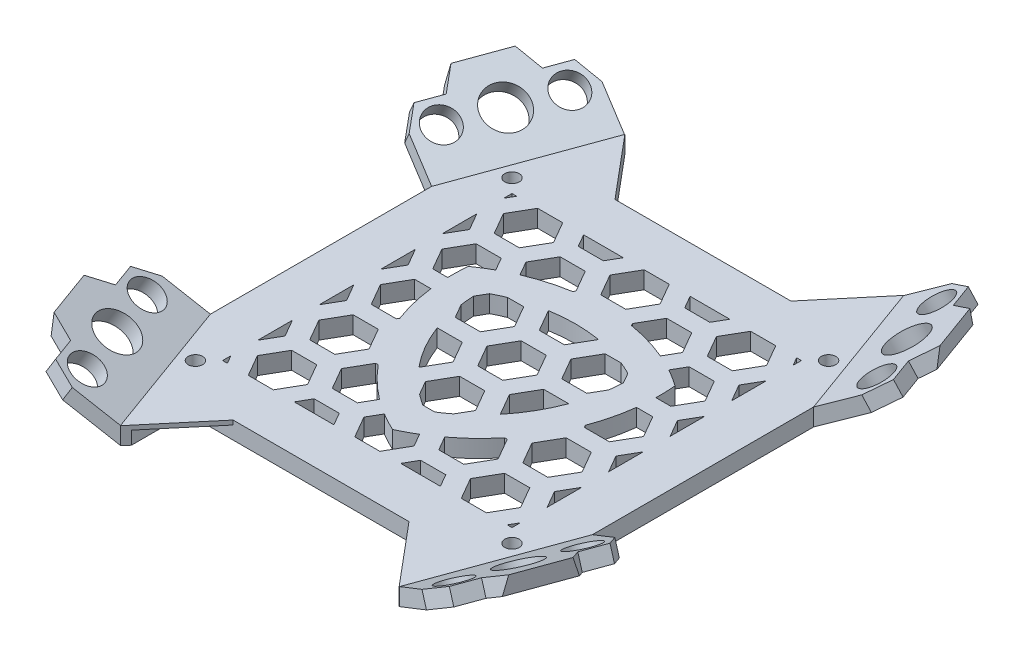
SolidWorks part; units mm, degrees
ref_plane "Front Plane" through (0, 0, 0) normal (0, 0, 1) x (1, 0, 0)
ref_plane "Top Plane" through (0, 0, 0) normal (0, 1, 0) x (1, 0, 0)
ref_plane "Right Plane" through (0, 0, 0) normal (1, 0, 0) x (0, 0, -1)
sketch "Sketch11" plane through (0, 0, 0) normal (0, 1, 0) x (1, 0, 0)
  line L0 (-50, -50) -> (-50, 50)
  line L1 (-30.4059, -66) -> (30.4059, -66)
  line L2 (-66, -38.2239) -> (-66, 0)
  line L3 (-30.4059, 66) -> (30.4059, 66)
  line L4 (66, -38.2239) -> (66, 38.2239)
  line L5 (-66, -66) -> (66, 66) construction
  line L6 (-50, 50) -> (66, -66) construction
  line L7 (-50, 50) -> (50, 50)
  line L8 (50, -50) -> (50, 50)
  line L9 (-50, -50) -> (50, -50)
  line L18 (-66, 0) -> (-66, 38.2239) construction
  line L19 (-66, -66) -> (-66, 66) construction
  line L20 (66, 38.2239) -> (66, 66) construction
  line L21 (66, -66) -> (66, 66) construction
  line L22 (66, -66) -> (66, -38.2239) construction
  line L23 (-66, -66) -> (-66, -38.2239) construction
  line L24 (-48.1804, 87.1828) -> (-65.9654, 38.3188)
  line L27 (-48.1804, 87.1828) -> (-30.4059, 66)
  line L28 (-66, 38.2239) -> (-66, 66) construction
  line L29 (-66, 66) -> (66, 66) construction
  line L30 (0, -55) -> (0, 55) construction
  line L31 (48.1804, 87.1828) -> (30.4059, 66)
  line L32 (65.9654, 38.3188) -> (66, 38.2239)
  line L33 (48.1804, 87.1828) -> (65.9654, 38.3188)
  line L34 (-55, 0) -> (55, 0) construction
  line L35 (65.9654, -38.3188) -> (66, -38.2239)
  line L36 (48.1804, -87.1828) -> (65.9654, -38.3188)
  line L37 (48.1804, -87.1828) -> (30.4059, -66)
  line L38 (-48.1804, -87.1828) -> (-30.4059, -66)
  line L39 (-65.9654, -38.3188) -> (-66, -38.2239)
  line L40 (-48.1804, -87.1828) -> (-65.9654, -38.3188)
  line L41 (30.4059, 66) -> (66, 66) construction
  line L42 (30.4059, -66) -> (66, -66) construction
  line L43 (-66, -66) -> (66, -66) construction
  line L44 (-66, -66) -> (-30.4059, -66) construction
  line L45 (-66, 66) -> (-30.4059, 66) construction
  line L46 (-57.0729, 62.7508) -> (-66, 66) construction
  line L47 (-66, 38.2239) -> (-66, 0)
  line L48 (-66, 38.2239) -> (-65.9654, 38.3188)
  point P0 (0, 0)
  dimension "D1" = 132
  dimension "D2" = 9.5
  dimension "D4" = 52
  dimension "D5" = 60
  dimension "D8" = 20
  dimension "D3" = 16
extrude "Boss-Extrude6" add sketch "Sketch11" along normal blind 6
ref_plane "Plane1" through (4.5644, 0, -12.5405) normal (0.342, 0, -0.9397) x (0, -1, 0)
sketch "Sketch12" plane through (4.5644, 0, -12.5405) normal (0.342, 0, -0.9397) x (0, -1, 0)
  line L0 (-6, 75.093) -> (-21, 101.0738)
  line L1 (-21, 101.0738) -> (-15, 101.0738)
  line L2 (-15, 101.0738) -> (0, 75.093)
  line L4 (-6, 75.093) -> (0, 75.093)
  dimension "D1" = 6
  dimension "D2" = 30
  dimension "D3" = 60
extrude "Boss-Extrude7" add sketch "Sketch12" along normal blind 52
sketch "Sketch13" plane through (-15.1997, -28.0162, -5.5322) normal (0.4698, 0.866, 0.171) x (0.8827, -0.4609, -0.091)
  line L0 (-51.2289, 92.4122) -> (-71.3763, 44.4738) construction
  line L1 (-65.0573, 98.2239) -> (-37.4005, 86.6004) construction
  line L2 (-85.2046, 50.2856) -> (-57.5479, 38.6621) construction
  line L3 (-65.0573, 98.2239) -> (-85.2046, 50.2856) construction
  line L5 (-71.7755, 82.2385) -> (-85.1655, 50.3787) construction
  line L6 (-78.4863, 66.2709) -> (-73.2618, 59.3889)
  line L15 (-73.2618, 59.3889) -> (-76.6247, 51.3873)
  line L16 (-76.6247, 51.3873) -> (-71.3763, 44.4738)
  line L17 (-51.2289, 92.4122) -> (-59.8399, 91.3237)
  line L24 (-71.7755, 82.2385) -> (-63.2027, 83.3222)
  line L25 (-63.2027, 83.3222) -> (-59.8399, 91.3237)
  line L37 (-71.3763, 44.4738) -> (-85.2046, 50.2856)
  line L38 (-85.2046, 50.2856) -> (-78.4863, 66.2709)
  line L39 (-71.7755, 82.2385) -> (-65.0573, 98.2239)
  line L40 (-65.0573, 98.2239) -> (-51.2289, 92.4122)
  line L41 (-85.1655, 50.3787) -> (-78.4863, 66.2709) construction
  line L49 (-44.1188, 70.6151) -> (-49.3553, 77.5128) [skipped]
  line L51 (-60.0486, 83.7209) -> (-71.7755, 82.2385) [skipped]
  line L52 (-81.8532, 58.3033) -> (-86.159, 57.7591) construction
  line L53 (-54.1654, 46.6668) -> (-56.7896, 50.1235) construction
  line L54 (-62.7648, 45.5623) -> (-61.0832, 49.5633) [skipped]
  line L55 (-71.3763, 44.4738) -> (-62.7648, 45.5623) [skipped]
  line L56 (-68.0134, 52.4754) -> (-62.5566, 53.1651) construction
  line L57 (-50.8296, 54.6474) -> (-44.1188, 70.6151) [skipped]
  circle A0 centre (-68.0132, 52.4758) radius 5.5
  circle A1 centre (-61.3026, 68.443) radius 7
  circle A2 centre (-54.592, 84.4101) radius 5.5
  dimension "D1" = 11
  dimension "D2" = 11
  dimension "D3" = 14
  dimension "D6" = 17.3397
  dimension "D4" = 17.32
  dimension "D5" = 17.32
  dimension "D7" = 17.3397
  dimension "D8" = 120
  dimension "D9" = 30
  dimension "D10" = 7.4833
  dimension "D11" = 30
extrude "Cut-Extrude1" cut sketch "Sketch13" against normal through all
mirror "Mirror3" about plane through (0, 0, 0) normal (1, 0, 0) of "Cut-Extrude1", "Boss-Extrude7"
mirror "Mirror4" about plane through (0, 0, 0) normal (0, 0, 1) of "Boss-Extrude7", "Cut-Extrude1", "Mirror3"
sketch "Sketch18" plane through (0, 0, 66) normal (0, 0, 1) x (1, 0, 0)
  line L0 (0, 6) -> (0, 0) construction
  line L1 (-30.4059, 6) -> (30.4059, 6) construction
  line L2 (-30.4059, 0) -> (30.4059, 0) construction
  line L3 (0, 4.5) -> (-46.4059, 4.5)
  line L4 (-46.4059, 4.5) -> (-46.4059, 0)
  line L6 (-46.4059, 0) -> (46.4059, 0)
  line L7 (30.4059, 0) -> (48.1804, 0) construction
  line L8 (46.4059, 0) -> (46.4059, 4.5)
  line L9 (46.4059, 4.5) -> (0, 4.5)
  line L11 (-30.4059, 6) -> (-30.4059, 0) construction
  line L12 (30.4059, 6) -> (30.4059, 0) construction
  line L13 (-48.1804, 0) -> (-30.4059, 0) construction
  dimension "D1" = 16
  dimension "D2" = 16
  dimension "D3" = 1.5
extrude "Cut-Extrude2" cut sketch "Sketch18" along normal through all
sketch "Sketch19" plane through (0, 6, 0) normal (0, 1, 0) x (1, 0, 0)
  line L0 (30.4059, 66) -> (-30.4059, 66) construction
  line L3 (-66, 38.2239) -> (-66, -38.2239) construction
  line L4 (66, -38.2239) -> (66, 38.2239) construction
  circle A0 centre (-54.7, 54.7) radius 2.5
  circle A1 centre (54.7, 54.7) radius 2.5
  circle A2 centre (54.7, -54.7) radius 2.5
  circle A3 centre (-54.7, -54.7) radius 2.5
  point P15 (0, 0)
  dimension "D1" = 5
  dimension "D2" = 11.3
  dimension "D3" = 11.3
  dimension "D5" = 11.3
  dimension "D6" = 11.3
  dimension "D4" = 4
extrude "Cut-Extrude3" cut sketch "Sketch19" against normal through all
sketch "Sketch20" plane through (0, 0, 0) normal (0, 1, 0) x (1, 0, 0)
  line L0 (0, 0) -> (0, -28.75) construction
  line L1 (0, 0) -> (-25.9808, 15) construction
  line L2 (0, 0) -> (24.8982, 14.375) construction
  line L3 (8.6603, 21.25) -> (4.3301, 28.75) construction
  line L4 (8.6603, 0) -> (4.3301, 7.5)
  line L5 (4.3301, 7.5) -> (-4.3301, 7.5)
  line L6 (-4.3301, 7.5) -> (-8.6603, 0)
  line L7 (-8.6603, 0) -> (-4.3301, -7.5)
  line L8 (-4.3301, -7.5) -> (4.3301, -7.5)
  line L9 (4.3301, -7.5) -> (8.6603, 0)
  line L10 (4.3301, 28.75) -> (-4.3301, 28.75) construction
  line L11 (-4.3301, 28.75) -> (-8.6603, 21.25) construction
  line L12 (-8.6522, 21.2361) -> (-4.3301, 13.75)
  line L13 (-4.3301, 13.75) -> (4.3301, 13.75)
  line L14 (4.3301, 13.75) -> (8.6522, 21.2361)
  line L15 (8.6603, 42.5) -> (4.3301, 50)
  line L16 (4.3301, 50) -> (-4.3301, 50)
  line L17 (-4.3301, 50) -> (-8.6603, 42.5)
  line L18 (-8.6603, 42.5) -> (-4.3301, 35)
  line L19 (-4.3301, 35) -> (4.3301, 35)
  line L20 (4.3301, 35) -> (8.6603, 42.5)
  line L21 (-11.55, 0) -> (11.55, 0) construction
  line L22 (4.3301, -13.75) -> (8.6603, -21.25)
  line L23 (-4.3301, -13.75) -> (4.3301, -13.75)
  line L24 (-8.6603, -21.25) -> (-4.3301, -13.75)
  line L25 (-5.899, -26.0327) -> (-8.6603, -21.25)
  line L26 (2.0538, -28.75) -> (-2.0538, -28.75)
  line L27 (8.6603, -21.25) -> (5.899, -26.0327)
  line L28 (6.0762, -38.0243) -> (8.6603, -42.5)
  line L29 (-4.3301, -35) -> (4.3301, -35) construction
  line L30 (-8.6603, -42.5) -> (-6.0762, -38.0243)
  line L31 (-4.3301, -50) -> (-8.6603, -42.5)
  line L32 (4.3301, -50) -> (-4.3301, -50)
  line L33 (8.6603, -42.5) -> (4.3301, -50)
  line L34 (4.3301, -7.5) -> (4.3301, -13.75) construction
  line L35 (4.3301, -10.625) -> (18.403, -10.625) construction
  line L36 (11.2674, -34.5157) -> (14.0729, -39.375)
  line L37 (9.7428, -10.625) -> (14.0649, -18.1111)
  line L38 (18.403, -18.125) -> (22.7332, -18.125) construction
  line L39 (22.7332, -18.125) -> (24.8982, -14.375) construction
  line L40 (24.8982, -6.875) -> (22.7332, -3.125) construction
  line L41 (22.7171, -3.125) -> (14.0729, -3.125)
  line L42 (14.0729, -3.125) -> (9.7428, -10.625)
  line L43 (14.0729, -39.375) -> (22.7332, -39.375)
  line L44 (22.7332, -39.375) -> (27.0633, -31.875)
  line L45 (27.0633, -31.875) -> (22.7332, -24.375)
  line L46 (22.7332, -24.375) -> (21.8611, -24.375)
  line L47 (14.0729, -24.375) -> (9.7428, -31.875) construction
  line L48 (9.7428, -53.125) -> (14.0729, -60.625) construction
  line L49 (14.0729, -60.625) -> (22.7332, -60.625) construction
  line L50 (22.7332, -60.625) -> (27.0633, -53.125) construction
  line L51 (25.2591, -50) -> (22.7332, -45.625)
  line L52 (22.7332, -45.625) -> (14.0729, -45.625)
  line L53 (14.0729, -45.625) -> (11.547, -50)
  line L54 (14.0729, 45.625) -> (11.547, 50)
  line L55 (22.7332, 45.625) -> (14.0729, 45.625)
  line L56 (25.2591, 50) -> (22.7332, 45.625)
  line L57 (22.7332, 60.625) -> (27.0633, 53.125) construction
  line L58 (14.0729, 60.625) -> (22.7332, 60.625) construction
  line L59 (9.7428, 53.125) -> (14.0729, 60.625) construction
  line L60 (10.1788, 31.1197) -> (9.7428, 31.875)
  line L61 (22.7332, 24.375) -> (14.0729, 24.375) construction
  line L62 (27.0633, 31.875) -> (24.2578, 27.0157)
  line L63 (22.7332, 39.375) -> (27.0633, 31.875)
  line L64 (14.0729, 39.375) -> (22.7332, 39.375)
  line L65 (9.7428, 31.875) -> (14.0729, 39.375)
  line L66 (14.0729, 3.125) -> (9.7428, 10.625)
  line L67 (22.7332, 3.125) -> (14.0729, 3.125)
  line L68 (25.4945, 7.9077) -> (22.7332, 3.125)
  line L69 (23.8713, 16.1537) -> (25.9251, 12.5963)
  line L70 (14.0729, 18.125) -> (19.5955, 18.125)
  line L71 (9.7428, 10.625) -> (14.0729, 18.125)
  line L72 (45.4663, 42.5) -> (41.1362, 50)
  line L73 (41.1362, 50) -> (32.476, 50)
  line L74 (32.476, 50) -> (28.1458, 42.5)
  line L75 (28.1458, 42.5) -> (32.476, 35)
  line L76 (32.476, 35) -> (41.1362, 35)
  line L77 (41.1362, 35) -> (45.4663, 42.5)
  line L78 (50, 47.1475) -> (48.3531, 50)
  line L79 (46.5489, 53.125) -> (50.879, 60.625) construction
  line L80 (50.879, 60.625) -> (59.5392, 60.625) construction
  line L81 (59.5392, 60.625) -> (63.8694, 53.125) construction
  line L82 (63.8694, 53.125) -> (59.5392, 45.625) construction
  line L83 (59.5392, 45.625) -> (50.879, 45.625) construction
  line L84 (50, 25.8975) -> (46.5489, 31.875)
  line L85 (46.5489, 31.875) -> (50, 37.8525)
  line L86 (50.879, 39.375) -> (59.5392, 39.375) construction
  line L87 (59.5392, 39.375) -> (63.8694, 31.875) construction
  line L88 (63.8694, 31.875) -> (59.5392, 24.375) construction
  line L89 (59.5392, 24.375) -> (50.879, 24.375) construction
  line L90 (45.4663, 21.25) -> (41.1362, 28.75)
  line L91 (41.1362, 28.75) -> (32.476, 28.75)
  line L92 (32.476, 28.75) -> (29.8919, 24.2743)
  line L93 (28.1458, 21.25) -> (32.476, 13.75) construction
  line L94 (35.9682, 13.75) -> (41.1362, 13.75)
  line L95 (41.1362, 13.75) -> (45.4663, 21.25)
  line L96 (50, 4.6475) -> (46.5489, 10.625)
  line L97 (46.5489, 10.625) -> (50, 16.6025)
  line L98 (50.879, 18.125) -> (59.5392, 18.125) construction
  line L99 (59.5392, 18.125) -> (63.8694, 10.625) construction
  line L100 (63.8694, 10.625) -> (59.5392, 3.125) construction
  line L101 (59.5392, 3.125) -> (50.879, 3.125) construction
  line L102 (45.4663, 0) -> (41.1362, 7.5)
  line L103 (41.1362, 7.5) -> (35.5252, 7.5)
  line L104 (32.476, 7.5) -> (28.1458, 0) construction
  line L105 (32.0399, -6.7447) -> (32.476, -7.5)
  line L106 (32.476, -7.5) -> (41.1362, -7.5)
  line L107 (41.1362, -7.5) -> (45.4663, 0)
  line L108 (41.1362, -13.75) -> (45.4663, -21.25)
  line L109 (45.4663, -21.25) -> (41.1362, -28.75)
  line L110 (41.1362, -28.75) -> (32.476, -28.75)
  line L111 (32.476, -28.75) -> (28.1458, -21.25)
  line L112 (28.1458, -21.25) -> (32.476, -13.75)
  line L113 (32.476, -13.75) -> (41.1362, -13.75)
  line L114 (46.5489, -10.625) -> (50, -16.6025)
  line L115 (50.879, -18.125) -> (59.5392, -18.125) construction
  line L116 (59.5392, -18.125) -> (63.8694, -10.625) construction
  line L117 (63.8694, -10.625) -> (59.5392, -3.125) construction
  line L118 (59.5392, -3.125) -> (50.879, -3.125) construction
  line L119 (50, -4.6475) -> (46.5489, -10.625)
  line L120 (46.5489, -31.875) -> (50, -37.8525)
  line L121 (50.879, -39.375) -> (59.5392, -39.375) construction
  line L122 (59.5392, -39.375) -> (63.8694, -31.875) construction
  line L123 (63.8694, -31.875) -> (59.5392, -24.375) construction
  line L124 (59.5392, -24.375) -> (50.879, -24.375) construction
  line L125 (50, -25.8975) -> (46.5489, -31.875)
  line L126 (41.1362, -35) -> (45.4663, -42.5)
  line L127 (45.4663, -42.5) -> (41.1362, -50)
  line L128 (41.1362, -50) -> (32.476, -50)
  line L129 (32.476, -50) -> (28.1458, -42.5)
  line L130 (28.1458, -42.5) -> (32.476, -35)
  line L131 (32.476, -35) -> (41.1362, -35)
  line L132 (46.5489, -53.125) -> (50.879, -60.625) construction
  line L133 (50.879, -60.625) -> (59.5392, -60.625) construction
  line L134 (59.5392, -60.625) -> (63.8694, -53.125) construction
  line L135 (63.8694, -53.125) -> (59.5392, -45.625) construction
  line L136 (59.5392, -45.625) -> (50.879, -45.625) construction
  line L137 (50, -47.1475) -> (48.3531, -50)
  line L138 (0, -11.55) -> (0, 11.55) construction
  line L139 (-50, -47.1475) -> (-48.3531, -50)
  line L140 (-59.5392, -45.625) -> (-50.879, -45.625) construction
  line L141 (-63.8694, -53.125) -> (-59.5392, -45.625) construction
  line L142 (-59.5392, -60.625) -> (-63.8694, -53.125) construction
  line L143 (-50.879, -60.625) -> (-59.5392, -60.625) construction
  line L144 (-46.5489, -53.125) -> (-50.879, -60.625) construction
  line L145 (-50, -25.8975) -> (-46.5489, -31.875)
  line L146 (-59.5392, -24.375) -> (-50.879, -24.375) construction
  line L147 (-63.8694, -31.875) -> (-59.5392, -24.375) construction
  line L148 (-59.5392, -39.375) -> (-63.8694, -31.875) construction
  line L149 (-50.879, -39.375) -> (-59.5392, -39.375) construction
  line L150 (-46.5489, -31.875) -> (-50, -37.8525)
  line L151 (-50, -4.6475) -> (-46.5489, -10.625)
  line L152 (-59.5392, -3.125) -> (-50.879, -3.125) construction
  line L153 (-63.8694, -10.625) -> (-59.5392, -3.125) construction
  line L154 (-59.5392, -18.125) -> (-63.8694, -10.625) construction
  line L155 (-50.879, -18.125) -> (-59.5392, -18.125) construction
  line L156 (-46.5489, -10.625) -> (-50, -16.6025)
  line L157 (-59.5392, 3.125) -> (-50.879, 3.125) construction
  line L158 (-63.8694, 10.625) -> (-59.5392, 3.125) construction
  line L159 (-59.5392, 18.125) -> (-63.8694, 10.625) construction
  line L160 (-50.879, 18.125) -> (-59.5392, 18.125) construction
  line L161 (-46.5489, 10.625) -> (-50, 16.6025)
  line L162 (-50, 4.6475) -> (-46.5489, 10.625)
  line L163 (-59.5392, 24.375) -> (-50.879, 24.375) construction
  line L164 (-63.8694, 31.875) -> (-59.5392, 24.375) construction
  line L165 (-59.5392, 39.375) -> (-63.8694, 31.875) construction
  line L166 (-50.879, 39.375) -> (-59.5392, 39.375) construction
  line L167 (-46.5489, 31.875) -> (-50, 37.8525)
  line L168 (-50, 25.8975) -> (-46.5489, 31.875)
  line L169 (-59.5392, 45.625) -> (-50.879, 45.625) construction
  line L170 (-63.8694, 53.125) -> (-59.5392, 45.625) construction
  line L171 (-59.5392, 60.625) -> (-63.8694, 53.125) construction
  line L172 (-50.879, 60.625) -> (-59.5392, 60.625) construction
  line L173 (-46.5489, 53.125) -> (-50.879, 60.625) construction
  line L174 (-50, 47.1475) -> (-48.3531, 50)
  line L175 (-41.1362, 35) -> (-45.4663, 42.5)
  line L176 (-32.476, 35) -> (-41.1362, 35)
  line L177 (-28.1458, 42.5) -> (-32.476, 35)
  line L178 (-32.476, 50) -> (-28.1458, 42.5)
  line L179 (-41.1362, 50) -> (-32.476, 50)
  line L180 (-45.4663, 42.5) -> (-41.1362, 50)
  line L181 (-41.1362, 13.75) -> (-45.4663, 21.25)
  line L182 (-35.9682, 13.75) -> (-41.1362, 13.75)
  line L183 (-28.1458, 21.25) -> (-32.476, 13.75) construction
  line L184 (-32.476, 28.75) -> (-29.8919, 24.2743)
  line L185 (-41.1362, 28.75) -> (-32.476, 28.75)
  line L186 (-45.4663, 21.25) -> (-41.1362, 28.75)
  line L187 (-41.1362, -7.5) -> (-45.4663, 0)
  line L188 (-32.476, -7.5) -> (-41.1362, -7.5)
  line L189 (-32.0399, -6.7447) -> (-32.476, -7.5)
  line L190 (-32.476, 7.5) -> (-28.1458, 0) construction
  line L191 (-41.1362, 7.5) -> (-35.5252, 7.5)
  line L192 (-45.4663, 0) -> (-41.1362, 7.5)
  line L193 (-32.476, -13.75) -> (-41.1362, -13.75)
  line L194 (-28.1458, -21.25) -> (-32.476, -13.75)
  line L195 (-32.476, -28.75) -> (-28.1458, -21.25)
  line L196 (-41.1362, -28.75) -> (-32.476, -28.75)
  line L197 (-45.4663, -21.25) -> (-41.1362, -28.75)
  line L198 (-41.1362, -13.75) -> (-45.4663, -21.25)
  line L199 (-32.476, -35) -> (-41.1362, -35)
  line L200 (-28.1458, -42.5) -> (-32.476, -35)
  line L201 (-32.476, -50) -> (-28.1458, -42.5)
  line L202 (-41.1362, -50) -> (-32.476, -50) construction
  line L203 (-45.4663, -42.5) -> (-41.1362, -50)
  line L204 (-41.1362, -35) -> (-45.4663, -42.5)
  line L205 (-14.0729, -45.625) -> (-11.547, -50)
  line L206 (-22.7332, -45.625) -> (-14.0729, -45.625)
  line L207 (-25.2591, -50) -> (-22.7332, -45.625)
  line L208 (-22.7332, -60.625) -> (-27.0633, -53.125) construction
  line L209 (-14.0729, -60.625) -> (-22.7332, -60.625) construction
  line L210 (-9.7428, -53.125) -> (-14.0729, -60.625) construction
  line L211 (-14.0729, -24.375) -> (-9.7428, -31.875) construction
  line L212 (-22.7332, -24.375) -> (-21.8611, -24.375)
  line L213 (-27.0633, -31.875) -> (-22.7332, -24.375)
  line L214 (-22.7332, -39.375) -> (-27.0633, -31.875)
  line L215 (-14.0729, -39.375) -> (-22.7332, -39.375)
  line L216 (-11.2674, -34.5157) -> (-14.0729, -39.375)
  line L217 (-14.0729, -3.125) -> (-9.7428, -10.625)
  line L218 (-22.7171, -3.125) -> (-14.0729, -3.125)
  line L219 (-27.0633, -10.625) -> (-22.7332, -3.125) construction
  line L220 (-22.7332, -18.125) -> (-27.0633, -10.625) construction
  line L221 (-14.0729, -18.125) -> (-22.7332, -18.125) construction
  line L222 (-9.7428, -10.625) -> (-14.0649, -18.1111)
  line L223 (-22.7332, 3.125) -> (-14.0729, 3.125)
  line L224 (-25.4945, 7.9077) -> (-22.7332, 3.125)
  line L225 (-23.8713, 16.1537) -> (-25.9251, 12.5963)
  line L226 (-14.0729, 18.125) -> (-19.5955, 18.125)
  line L227 (-9.7428, 10.625) -> (-14.0729, 18.125)
  line L228 (-14.0729, 3.125) -> (-9.7428, 10.625)
  line L229 (-22.7332, 24.375) -> (-14.0729, 24.375) construction
  line L230 (-27.0633, 31.875) -> (-24.2578, 27.0157)
  line L231 (-22.7332, 39.375) -> (-27.0633, 31.875)
  line L232 (-14.0729, 39.375) -> (-22.7332, 39.375)
  line L233 (-9.7428, 31.875) -> (-14.0729, 39.375)
  line L234 (-10.1788, 31.1197) -> (-9.7428, 31.875)
  line L235 (-22.7332, 45.625) -> (-14.0729, 45.625)
  line L236 (-25.2591, 50) -> (-22.7332, 45.625)
  line L237 (-22.7332, 60.625) -> (-27.0633, 53.125) construction
  line L238 (-14.0729, 60.625) -> (-22.7332, 60.625) construction
  line L239 (-9.7428, 53.125) -> (-14.0729, 60.625) construction
  line L240 (-14.0729, 45.625) -> (-11.547, 50)
  line L241 (-48.3531, 50) -> (-46.5489, 53.125) construction
  line L242 (-48.3531, 50) -> (-25.2591, 50)
  line L243 (-50, 47.1475) -> (-50, 37.8525)
  line L244 (-48.3531, -50) -> (-25.2591, -50) construction
  line L245 (50, 47.1475) -> (50, 37.8525)
  line L246 (-50.879, 45.625) -> (-50, 47.1475) construction
  line L247 (-50, 50) -> (-50, 47.1475) construction
  line L248 (-50, 50) -> (-48.3531, 50) construction
  line L249 (-50, 37.8525) -> (-50.879, 39.375) construction
  line L250 (-50.879, 24.375) -> (-50, 25.8975) construction
  line L251 (-50, 16.6025) -> (-50.879, 18.125) construction
  line L252 (-50.879, 3.125) -> (-50, 4.6475) construction
  line L253 (-50.879, -3.125) -> (-50, -4.6475) construction
  line L254 (-50, -16.6025) -> (-50.879, -18.125) construction
  line L255 (-50, 37.8525) -> (-50, 25.8975) construction
  line L256 (-50, 25.8975) -> (-50, 16.6025)
  line L257 (-50, 16.6025) -> (-50, 4.6475) construction
  line L258 (-50, 4.6475) -> (-50, -4.6475)
  line L259 (-50, -4.6475) -> (-50, -16.6025) construction
  line L260 (-50, -16.6025) -> (-50, -25.8975)
  line L261 (-50, -25.8975) -> (-50, -37.8525) construction
  line L262 (-50, -37.8525) -> (-50, -47.1475)
  line L263 (-50.879, -24.375) -> (-50, -25.8975) construction
  line L264 (-50, -37.8525) -> (-50.879, -39.375) construction
  line L265 (-50.879, -45.625) -> (-50, -47.1475) construction
  line L266 (-48.3531, -50) -> (-46.5489, -53.125) construction
  line L267 (-50, -50) -> (-48.3531, -50) construction
  line L268 (-50, -47.1475) -> (-50, -50) construction
  line L269 (-27.0633, -53.125) -> (-25.2591, -50) construction
  line L270 (-11.547, -50) -> (-9.7428, -53.125) construction
  line L271 (11.547, -50) -> (9.7428, -53.125) construction
  line L272 (27.0633, -53.125) -> (25.2591, -50) construction
  line L273 (11.547, -50) -> (25.2591, -50) construction
  line L274 (25.2591, -50) -> (48.3531, -50)
  line L275 (-25.2591, -50) -> (-11.547, -50) construction
  line L276 (-11.547, -50) -> (11.547, -50)
  line L277 (48.3531, -50) -> (46.5489, -53.125) construction
  line L278 (50.879, -45.625) -> (50, -47.1475) construction
  line L279 (50, -47.1475) -> (50, -50) construction
  line L280 (48.3531, -50) -> (50, -50) construction
  line L281 (50.879, -24.375) -> (50, -25.8975) construction
  line L282 (50, -37.8525) -> (50.879, -39.375) construction
  line L283 (50, -25.8975) -> (50, -37.8525) construction
  line L284 (50, -37.8525) -> (50, -47.1475)
  line L285 (50.879, -3.125) -> (50, -4.6475) construction
  line L286 (50, -16.6025) -> (50.879, -18.125) construction
  line L287 (50, -4.6475) -> (50, -16.6025) construction
  line L288 (50, -16.6025) -> (50, -25.8975)
  line L289 (50, 16.6025) -> (50.879, 18.125) construction
  line L290 (50.879, 3.125) -> (50, 4.6475) construction
  line L291 (50, 16.6025) -> (50, 4.6475) construction
  line L292 (50, 4.6475) -> (50, -4.6475)
  line L293 (50, 37.8525) -> (50.879, 39.375) construction
  line L294 (50.879, 24.375) -> (50, 25.8975) construction
  line L295 (50, 37.8525) -> (50, 25.8975) construction
  line L296 (50, 25.8975) -> (50, 16.6025)
  line L297 (50.879, 45.625) -> (50, 47.1475) construction
  line L298 (48.3531, 50) -> (46.5489, 53.125) construction
  line L299 (48.3531, 50) -> (50, 50) construction
  line L300 (50, 50) -> (50, 47.1475) construction
  line L301 (11.547, 50) -> (9.7428, 53.125) construction
  line L302 (27.0633, 53.125) -> (25.2591, 50) construction
  line L303 (11.547, 50) -> (25.2591, 50) construction
  line L304 (25.2591, 50) -> (48.3531, 50)
  line L305 (-11.547, 50) -> (-9.7428, 53.125) construction
  line L306 (-27.0633, 53.125) -> (-25.2591, 50) construction
  line L307 (-25.2591, 50) -> (-11.547, 50) construction
  line L308 (-11.547, 50) -> (11.547, 50)
  line L309 (-14.0729, 24.375) -> (-10.1788, 31.1197) construction
  line L310 (-24.2578, 27.0157) -> (-22.7332, 24.375) construction
  line L311 (14.0729, 24.375) -> (10.1788, 31.1197) construction
  line L312 (24.2578, 27.0157) -> (22.7332, 24.375) construction
  line L313 (29.8919, 24.2743) -> (28.1458, 21.25) construction
  line L314 (32.476, 13.75) -> (35.9682, 13.75) construction
  line L315 (35.5252, 7.5) -> (32.476, 7.5) construction
  line L316 (28.1458, 0) -> (32.0399, -6.7447) construction
  line L317 (21.8611, -24.375) -> (14.0729, -24.375) construction
  line L318 (9.7428, -31.875) -> (11.2674, -34.5157) construction
  line L319 (-6.0762, -38.0243) -> (-4.3301, -35) construction
  line L320 (4.3301, -35) -> (6.0762, -38.0243) construction
  line L321 (-21.8611, -24.375) -> (-14.0729, -24.375) construction
  line L322 (-9.7428, -31.875) -> (-11.2674, -34.5157) construction
  line L323 (-28.1458, 0) -> (-32.0399, -6.7447) construction
  line L324 (-35.5252, 7.5) -> (-32.476, 7.5) construction
  line L325 (-32.476, 13.75) -> (-35.9682, 13.75) construction
  line L326 (-29.8919, 24.2743) -> (-28.1458, 21.25) construction
  line L327 (-22.7332, 18.125) -> (-23.8713, 16.1537) construction
  line L328 (-19.5955, 18.125) -> (-22.7332, 18.125) construction
  line L329 (-25.9251, 12.5963) -> (-27.0633, 10.625) construction
  line L330 (-27.0633, 10.625) -> (-25.4945, 7.9077) construction
  line L331 (-4.3301, -28.75) -> (-5.899, -26.0327) construction
  line L332 (-2.0538, -28.75) -> (-4.3301, -28.75) construction
  line L333 (4.3301, -28.75) -> (2.0538, -28.75) construction
  line L334 (5.899, -26.0327) -> (4.3301, -28.75) construction
  line L335 (0, -28.75) -> (0, -30) construction
  line L336 (14.0729, -18.125) -> (18.403, -18.125) construction
  line L337 (27.0633, -10.625) -> (24.8982, -6.875) construction
  line L338 (24.8982, -14.375) -> (27.0633, -10.625) construction
  line L339 (25.9251, 12.5963) -> (27.0633, 10.625) construction
  line L340 (27.0633, 10.625) -> (25.4945, 7.9077) construction
  line L341 (24.8982, 14.375) -> (25.9808, 15) construction
  line L342 (22.7332, 18.125) -> (23.8713, 16.1537) construction
  line L343 (19.5955, 18.125) -> (22.7332, 18.125) construction
  line L344 (-8.6603, 21.25) -> (-8.6522, 21.2361) construction
  line L345 (8.6522, 21.2361) -> (8.6603, 21.25) construction
  line L346 (22.7332, -3.125) -> (22.7171, -3.125) construction
  line L347 (14.0649, -18.1111) -> (14.0729, -18.125) construction
  line L348 (-14.0649, -18.1111) -> (-14.0729, -18.125) construction
  line L349 (-22.7332, -3.125) -> (-22.7171, -3.125) construction
  line L350 (-41.1362, -50) -> (-48.3531, -50)
  line L351 (-32.476, -50) -> (-25.2591, -50)
  arc A0 (2.0538, -28.75) -> (5.899, -26.0327) centre (-25.9808, 15) ccw
  arc A1 (-25.9251, 12.5963) -> (-25.4945, 7.9077) centre (25.9808, 15) ccw
  arc A2 (23.8713, 16.1537) -> (19.5955, 18.125) centre (0, -30) ccw
  arc A3 (0, -41.2515) -> (6.0762, -38.0243) centre (-25.9808, 15) ccw
  arc A4 (35.7248, 20.6257) -> (29.8919, 24.2743) centre (0, -30) ccw
  arc A5 (-35.7248, 20.6257) -> (-35.9682, 13.75) centre (25.9808, 15) ccw
  circle A6 centre (0, 0) radius 7.5 construction
  arc A7 (18.403, -18.125) -> (24.8982, -14.375) centre (18.403, -10.625) ccw construction
  arc A8 (-24.2578, 27.0157) -> (-29.8919, 24.2743) centre (0, -30) ccw construction
  arc A9 (-29.8919, 24.2743) -> (-35.7248, 20.6257) centre (0, -30) ccw
  arc A10 (35.7248, 20.6257) -> (-35.7248, 20.6257) centre (0, -30) ccw construction
  arc A11 (10.1788, 31.1197) -> (-10.1788, 31.1197) centre (0, -30) ccw construction
  arc A12 (-10.1788, 31.1197) -> (-24.2578, 27.0157) centre (0, -30) ccw
  arc A13 (29.8919, 24.2743) -> (24.2578, 27.0157) centre (0, -30) ccw construction
  arc A14 (24.2578, 27.0157) -> (10.1788, 31.1197) centre (0, -30) ccw
  arc A15 (-8.6522, 21.2361) -> (-19.5955, 18.125) centre (0, -30) ccw construction
  arc A16 (-19.5955, 18.125) -> (-23.8713, 16.1537) centre (0, -30) ccw
  arc A17 (25.9808, 15) -> (-25.9808, 15) centre (0, -30) ccw construction
  arc A18 (19.5955, 18.125) -> (8.6522, 21.2361) centre (0, -30) ccw construction
  arc A19 (8.6522, 21.2361) -> (-8.6522, 21.2361) centre (0, -30) ccw
  arc A20 (35.5252, 7.5) -> (35.9682, 13.75) centre (-25.9808, 15) ccw construction
  arc A21 (35.9682, 13.75) -> (35.7248, 20.6257) centre (-25.9808, 15) ccw
  arc A22 (0, -41.2515) -> (35.7248, 20.6257) centre (-25.9808, 15) ccw construction
  arc A23 (21.8611, -24.375) -> (32.0399, -6.7447) centre (-25.9808, 15) ccw construction
  arc A24 (32.0399, -6.7447) -> (35.5252, 7.5) centre (-25.9808, 15) ccw
  arc A25 (6.0762, -38.0243) -> (11.2674, -34.5157) centre (-25.9808, 15) ccw construction
  arc A26 (11.2674, -34.5157) -> (21.8611, -24.375) centre (-25.9808, 15) ccw
  arc A27 (-11.2674, -34.5157) -> (-6.0762, -38.0243) centre (25.9808, 15) ccw construction
  arc A28 (-6.0762, -38.0243) -> (0, -41.2515) centre (25.9808, 15) ccw
  arc A29 (-35.7248, 20.6257) -> (0, -41.2515) centre (25.9808, 15) ccw construction
  arc A30 (-32.0399, -6.7447) -> (-21.8611, -24.375) centre (25.9808, 15) ccw construction
  arc A31 (-21.8611, -24.375) -> (-11.2674, -34.5157) centre (25.9808, 15) ccw
  arc A32 (-35.9682, 13.75) -> (-35.5252, 7.5) centre (25.9808, 15) ccw construction
  arc A33 (-35.5252, 7.5) -> (-32.0399, -6.7447) centre (25.9808, 15) ccw
  arc A34 (-23.8713, 16.1537) -> (-25.9808, 15) centre (0, -30) ccw construction
  arc A35 (-25.9808, 15) -> (-25.9251, 12.5963) centre (25.9808, 15) ccw construction
  arc A36 (-25.9808, 15) -> (0, -30) centre (25.9808, 15) ccw construction
  arc A37 (-25.4945, 7.9077) -> (-22.7171, -3.125) centre (25.9808, 15) ccw construction
  arc A38 (-22.7171, -3.125) -> (-14.0649, -18.1111) centre (25.9808, 15) ccw
  arc A39 (-14.0649, -18.1111) -> (-5.899, -26.0327) centre (25.9808, 15) ccw construction
  arc A40 (-5.899, -26.0327) -> (-2.0538, -28.75) centre (25.9808, 15) ccw
  arc A41 (-2.0538, -28.75) -> (0, -30) centre (25.9808, 15) ccw construction
  arc A42 (0, -30) -> (2.0538, -28.75) centre (-25.9808, 15) ccw construction
  arc A43 (0, -30) -> (25.9808, 15) centre (-25.9808, 15) ccw construction
  arc A44 (5.899, -26.0327) -> (14.0649, -18.1111) centre (-25.9808, 15) ccw construction
  arc A45 (14.0649, -18.1111) -> (22.7171, -3.125) centre (-25.9808, 15) ccw
  arc A46 (14.7992, -17.2024) -> (18.403, -18.125) centre (18.403, -10.625) ccw construction
  arc A47 (24.8982, -14.375) -> (24.8982, -6.875) centre (18.403, -10.625) ccw construction
  arc A48 (22.2973, -4.2153) -> (14.7992, -17.2024) centre (18.403, -10.625) ccw construction
  arc A49 (22.7171, -3.125) -> (25.4945, 7.9077) centre (-25.9808, 15) ccw construction
  arc A50 (25.4945, 7.9077) -> (25.9251, 12.5963) centre (-25.9808, 15) ccw
  arc A51 (24.8982, -6.875) -> (22.2973, -4.2153) centre (18.403, -10.625) ccw construction
  arc A52 (25.9251, 12.5963) -> (25.9808, 15) centre (-25.9808, 15) ccw construction
  arc A53 (25.9808, 15) -> (23.8713, 16.1537) centre (0, -30) ccw construction
  dimension "D1" = 10
  dimension "D2" = 30
  dimension "D3" = 15
  dimension "D4" = 120
  dimension "D5" = 120
  dimension "D6" = 3
  dimension "D7" = 6.25
  dimension "D8" = 6.25
  dimension "D9" = 15
  dimension "D11" = 6.25
  dimension "D13" = 6.25
  dimension "D10" = 3
  dimension "D12" = 2
extrude "Boss-Extrude9" add sketch "Sketch20" along normal up to surface (6 mm away) contours L351 L207 L206 L205 L276 L53 L52 L51 L274 L137 L284 L120 L125 L288 L114 L119 L292 L96 L97 L296 L84 L85 L245 L78 L304 L56 L55 L54 L308 L240 L235 L236 L242 L174 L243 L167 L168 L256 L161 L162 L258 L151 L156 L260 L145 L150 L262 L139 L350 L203 L204 L199 L200 L201 | L175 L180 L179 L178 L177 L176 | L15 L16 L17 L18 L19 L20 | L60 L65 L64 L63 L62 A14 | L72 L73 L74 L75 L76 L77 | A4 L92 L91 L90 L95 L94 A21 | L13 L14 A19 L12 | L230 A12 L234 L233 L232 L231 | L184 A9 A5 L182 L181 L186 L185 | L189 L188 L187 L192 L191 A33 | L225 A1 L224 L223 L228 L227 L226 A16 | L4 L5 L6 L7 L8 L9 | L69 A50 L68 L67 L66 L71 L70 A2 | L103 A24 L105 L106 L107 L102 | L108 L109 L110 L111 L112 L113 | L37 A45 L41 L42 | L26 A40 L25 L24 L23 L22 L27 A0 | L218 L217 L222 A38 | L193 L198 L197 L196 L195 L194 | L216 L215 L214 L213 L212 A31 | A3 L28 L33 L32 L31 L30 A28 | L46 A26 L36 L43 L44 L45 | L126 L127 L128 L129 L130 L131 up to face at (-54.7, 6, 57.2)
